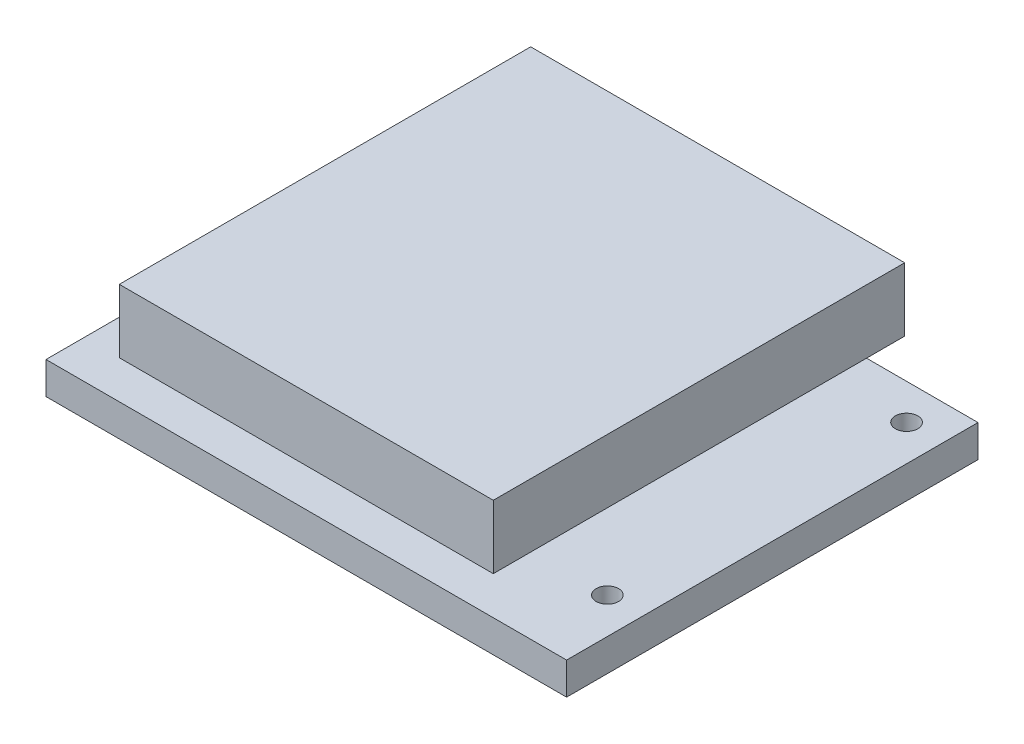
SolidWorks part; units mm, degrees
ref_plane "Front Plane" through (0, 0, 0) normal (0, 0, 1) x (1, 0, 0)
ref_plane "Top Plane" through (0, 0, 0) normal (0, 1, 0) x (1, 0, 0)
ref_plane "Right Plane" through (0, 0, 0) normal (1, 0, 0) x (0, 0, -1)
sketch "Sketch1" plane through (0, 0, 0) normal (0, 1, 0) x (1, 0, 0)
  line L0 (0, -55) -> (0, 55) construction
  line L1 (-34.8, -27.5) -> (34.8, -27.5)
  line L2 (-34.8, -27.5) -> (-34.8, 27.5)
  line L3 (-34.8, 27.5) -> (34.8, 27.5)
  line L4 (34.8, -27.5) -> (34.8, 27.5)
  line L5 (-34.8, -27.5) -> (34.8, 27.5) construction
  line L6 (-34.8, 27.5) -> (34.8, -27.5) construction
  circle A0 centre (30, 22.75) radius 1.5
  circle A1 centre (30, -17.25) radius 1.5
  circle A2 centre (-30, -17.25) radius 1.5
  circle A3 centre (-30, 22.75) radius 1.5
  point P0 (0, 0)
  point P8 (0, 0)
  dimension "D3" = 3
  dimension "D5" = 3
  dimension "D6" = 40
  dimension "D1" = 55
  dimension "D2" = 69.6
  dimension "D4" = 4.75
  dimension "D7" = 60
  dimension "D8" = 60
extrude "Boss-Extrude1" add sketch "Sketch1" along normal blind 4.3
ref_plane "Plane1" through (0, 9.4, 0) normal (0, 1, 0) x (1, 0, 0)
sketch "Sketch3" plane through (0, 9.4, 0) normal (0, 1, 0) x (1, 0, 0)
  line L0 (34.8, 27.5) -> (-34.8, 27.5) construction
  line L1 (-25, -27.5) -> (25, -27.5)
  line L2 (-25, -27.5) -> (-25, 27.5)
  line L3 (-25, 27.5) -> (25, 27.5)
  line L4 (25, -27.5) -> (25, 27.5)
  line L5 (-25, -27.5) -> (25, 27.5) construction
  line L6 (-25, 27.5) -> (25, -27.5) construction
  point P0 (0, 0)
  dimension "D1" = 50
extrude "Boss-Extrude2" add sketch "Sketch3" along normal blind 1.5 separate body contours L3 L4 L1 L2
sketch "Sketch5" plane through (0, 10.9, 0) normal (0, 1, 0) x (1, 0, 0)
  line L1 (-25, -27.5) -> (25, -27.5)
  line L2 (-25, -27.5) -> (-25, 27.5)
  line L3 (-25, 27.5) -> (25, 27.5)
  line L4 (25, -27.5) -> (25, 27.5)
  line L5 (-25, -27.5) -> (25, 27.5) construction
  line L6 (-25, 27.5) -> (25, -27.5) construction
  point P0 (0, 0)
extrude "Boss-Extrude3" add sketch "Sketch5" along normal blind 7
